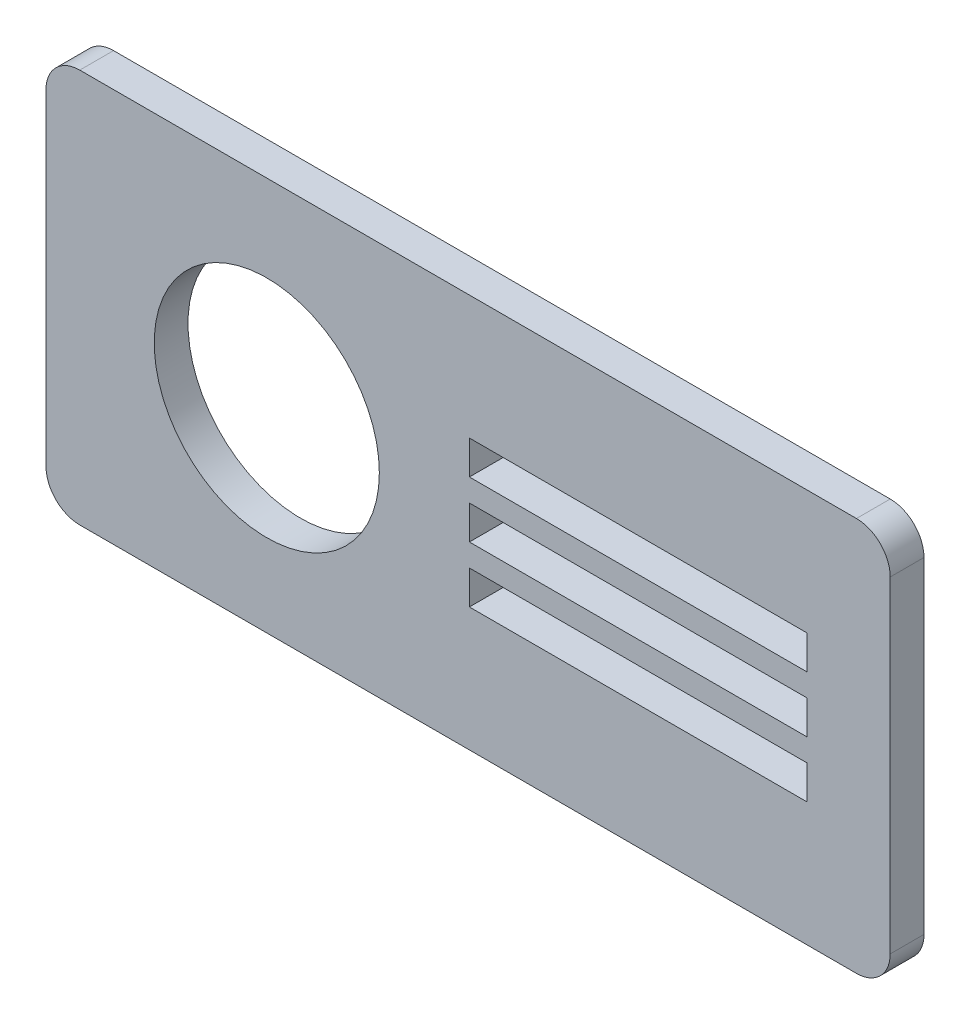
SolidWorks part; units mm, degrees
ref_plane "Front Plane" through (0, 0, 0) normal (0, 0, 1) x (1, 0, 0)
ref_plane "Top Plane" through (0, 0, 0) normal (0, 1, 0) x (1, 0, 0)
ref_plane "Right Plane" through (0, 0, 0) normal (1, 0, 0) x (0, 0, -1)
sketch "Sketch1" plane through (0, 0, 0) normal (0, 0, 1) x (1, 0, 0)
  line L0 (-78.5, 101.2037) -> (-147.5, 101.2037) construction
  line L1 (-75.5, 69.2037) -> (-75.5, 98.2037) construction
  line L2 (-147.5, 66.2037) -> (-78.5, 66.2037) construction
  line L3 (-150.5, 98.2037) -> (-150.5, 69.2037) construction
  line L4 (-78.5, 101.2037) -> (-147.5, 101.2037)
  line L5 (-75.5, 69.2037) -> (-75.5, 98.2037)
  line L6 (-147.5, 66.2037) -> (-78.5, 66.2037)
  line L7 (-150.5, 98.2037) -> (-150.5, 69.2037)
  line L8 (-130.8892, 83.5278) -> (-130.8863, 83.5278) construction
  line L9 (-150.5, 83.7037) -> (-75.5, 83.7037) construction
  line L11 (-112.8863, 85.2037) -> (-82.8863, 85.2037)
  line L12 (-112.8863, 85.2037) -> (-112.8863, 82.2037)
  line L13 (-112.8863, 82.2037) -> (-82.8863, 82.2037)
  line L14 (-82.8863, 85.2037) -> (-82.8863, 82.2037)
  line L15 (-112.8863, 87.2037) -> (-82.8863, 87.2037)
  line L16 (-112.8863, 87.2037) -> (-112.8863, 90.2037)
  line L17 (-112.8863, 90.2037) -> (-82.8863, 90.2037)
  line L18 (-82.8863, 87.2037) -> (-82.8863, 90.2037)
  line L19 (-112.8863, 80.2037) -> (-82.8863, 80.2037)
  line L20 (-112.8863, 80.2037) -> (-112.8863, 77.2037)
  line L21 (-112.8863, 77.2037) -> (-82.8863, 77.2037)
  line L22 (-82.8863, 80.2037) -> (-82.8863, 77.2037)
  arc A0 (-75.5, 98.2037) -> (-78.5, 101.2037) centre (-78.5, 98.2037) ccw construction
  arc A1 (-78.5, 66.2037) -> (-75.5, 69.2037) centre (-78.5, 69.2037) ccw construction
  arc A2 (-150.5, 69.2037) -> (-147.5, 66.2037) centre (-147.5, 69.2037) ccw construction
  arc A3 (-147.5, 101.2037) -> (-150.5, 98.2037) centre (-147.5, 98.2037) ccw construction
  arc A4 (-75.5, 98.2037) -> (-78.5, 101.2037) centre (-78.5, 98.2037) ccw
  arc A5 (-78.5, 66.2037) -> (-75.5, 69.2037) centre (-78.5, 69.2037) ccw
  arc A6 (-150.5, 69.2037) -> (-147.5, 66.2037) centre (-147.5, 69.2037) ccw
  arc A7 (-147.5, 101.2037) -> (-150.5, 98.2037) centre (-147.5, 98.2037) ccw
  circle A8 centre (-130.8863, 83.5278) radius 10
  dimension "D1" = 18
  dimension "D2" = 30
  dimension "D3" = 3
  dimension "D4" = 1.5
  dimension "D5" = 3
  dimension "D6" = 3
  dimension "D7" = 2
  dimension "D8" = 2
extrude "Boss-Extrude1" add sketch "Sketch1" against normal blind 3
